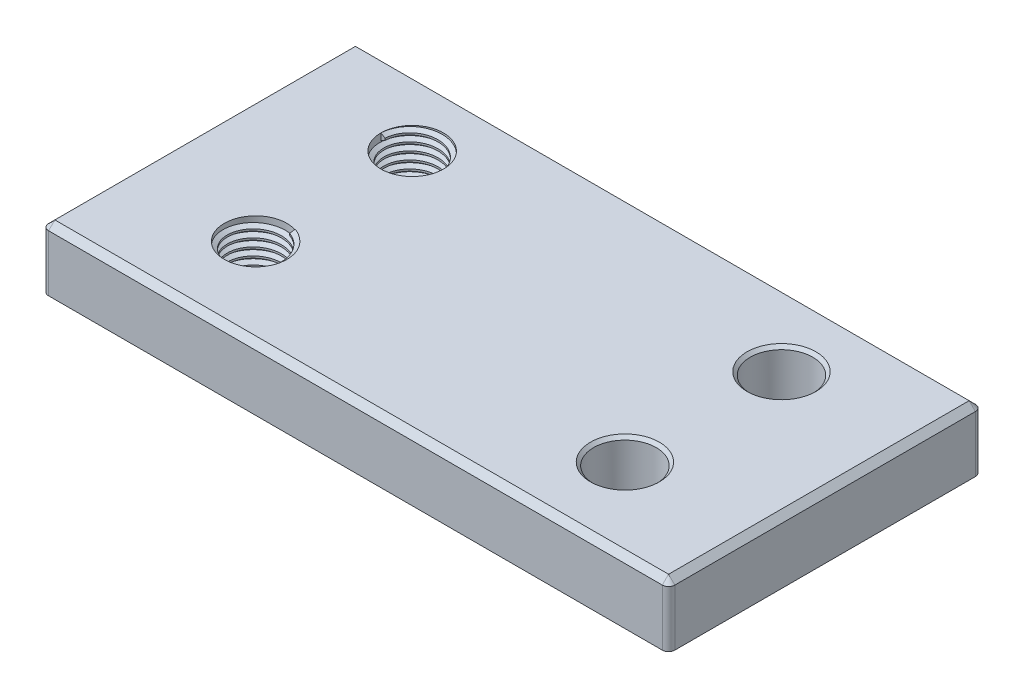
SolidWorks part; units mm, degrees
ref_plane "Alzado" through (0, 0, 0) normal (0, 0, 1) x (1, 0, 0)
ref_plane "Planta" through (0, 0, 0) normal (0, 1, 0) x (1, 0, 0)
ref_plane "Vista lateral" through (0, 0, 0) normal (1, 0, 0) x (0, 0, -1)
sketch "Croquis1" plane through (0, 0, 0) normal (0, 1, 0) x (1, 0, 0)
  line L1 (-49, 25) -> (49, 25)
  line L2 (-50, 24) -> (-50, -24)
  line L3 (-49, -25) -> (49, -25)
  line L4 (50, 24) -> (50, -24)
  line L5 (-50, 25) -> (50, -25) construction
  line L6 (-50, -25) -> (50, 25) construction
  arc A0 (49, 25) -> (50, 24) centre (49, 24) cw
  arc A1 (49, -25) -> (50, -24) centre (49, -24) ccw
  arc A2 (-50, -24) -> (-49, -25) centre (-49, -24) ccw
  arc A3 (-49, 25) -> (-50, 24) centre (-49, 24) ccw
  point P0 (0, 0)
  dimension "D3" = 1
  dimension "D1" = 100
  dimension "D2" = 50
extrude "Saliente-Extruir1" add sketch "Croquis1" along normal blind 10
chamfer "Chaflán1" distance 1 angle 45 8 edges at (-49.7071, 10, -24.7071) (-50, 10, 0) (-49.7071, 10, 24.7071) (0, 10, -25) (49.7071, 10, -24.7071) (50, 10, 0) (49.7071, 10, 24.7071) (0, 10, 25)
sketch "Croquis3" plane through (0, 10, 0) normal (0, 1, 0) x (1, 0, 0)
  line L0 (-50, -24) -> (-50, 24) construction
  circle A0 centre (-30, 14.062) radius 5
  circle A1 centre (-30, -10.938) radius 5
  dimension "D4" = 10
  dimension "D5" = 10
  dimension "D1" = 20
  dimension "D2" = 25
  dimension "D3" = 20
extrude "Cortar-Extruir1" cut sketch "Croquis3" against normal blind 10
thread "Rosca1" pitch 1.25 method extrude profile "Perfil de rosca1" start angle 0, offset 0, length 9, pitch 1.25, diameter 10
ref_plane "Plano2" through (-25, 0, 10.938) normal (0, 0, 1) x (1, 0, 0)
sketch "Perfil de rosca1" plane through (-25, 0, 10.938) normal (0, 0, 1) x (1, 0, 0)
  line L0 (0, 0) -> (0, 1.25) construction
  line L11 (0, 0) -> (0, 1.0937)
  line L12 (0, 1.0937) -> (-0.6766, 0.7031)
  line L13 (-0.6766, 0.7031) -> (-0.6766, 0.3906)
  line L15 (-0.6766, 0.3906) -> (0, 0)
  line L17 (-0.6766, 0.5469) -> (0, 0.5469) construction
  point P2 (0, 0)
  dimension "Pitch" = 1.25
  dimension "Profile_Angle" = 60
  dimension "Profile_Land" = 0.3125
  dimension "Profile_Height" = 0.6766
thread "Rosca3" pitch 1.25 method extrude profile "Perfil de rosca3" start angle 0, offset 0, length 9, pitch 1.25, diameter 10
ref_plane "Plano4" through (-35, 10, -14.062) normal (0, 0, 1) x (-1, 0, 0)
sketch "Perfil de rosca3" plane through (-35, 10, -14.062) normal (0, 0, 1) x (-1, 0, 0)
  line L0 (0, 0) -> (0, 1.25) construction
  line L11 (0, 0) -> (0, 1.0937)
  line L12 (0, 1.0937) -> (-0.6766, 0.7031)
  line L13 (-0.6766, 0.7031) -> (-0.6766, 0.3906)
  line L15 (-0.6766, 0.3906) -> (0, 0)
  line L17 (-0.6766, 0.5469) -> (0, 0.5469) construction
  point P2 (0, 0)
  dimension "Pitch" = 1.25
  dimension "Profile_Angle" = 60
  dimension "Profile_Land" = 0.3125
  dimension "Profile_Height" = 0.6766
sketch "Croquis14" plane through (0, 10, 0) normal (0, 1, 0) x (1, 0, 0)
  line L0 (50, 24) -> (50, -24) construction
  circle A0 centre (30, 13.0324) radius 5
  circle A1 centre (30, -11.9676) radius 5
  dimension "D4" = 10
  dimension "D5" = 10
  dimension "D1" = 25
  dimension "D2" = 20
  dimension "D3" = 20
extrude "Cortar-Extruir2" cut sketch "Croquis14" against normal blind 10
chamfer "Chaflán2" distance 0.5 angle 45 2 edges at (30, 10, 16.9676) (30, 10, -8.0324)
